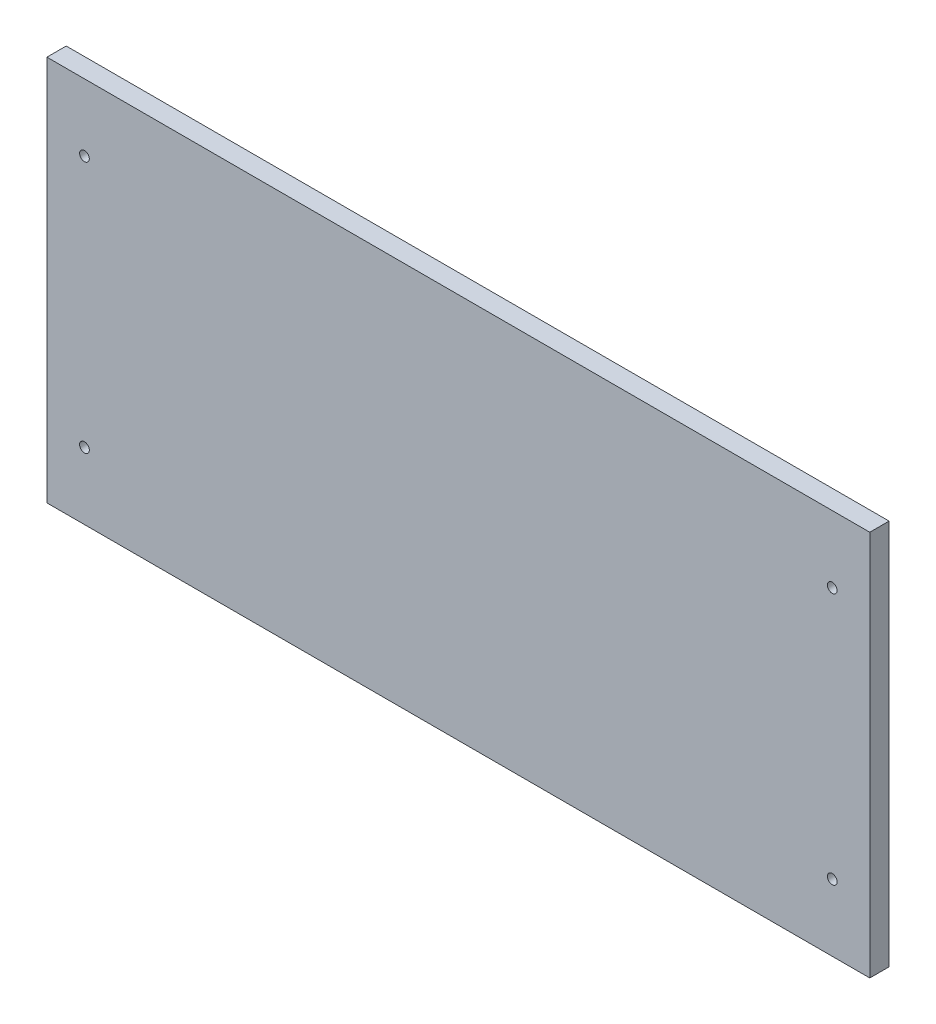
SolidWorks part; units mm, degrees
ref_plane "Front Plane" through (0, 0, 0) normal (0, 0, 1) x (1, 0, 0)
ref_plane "Top Plane" through (0, 0, 0) normal (0, 1, 0) x (1, 0, 0)
ref_plane "Right Plane" through (0, 0, 0) normal (1, 0, 0) x (0, 0, -1)
sketch "Sketch1" plane through (0, 0, 0) normal (0, 0, 1) x (1, 0, 0)
  line L0 (135.35, 127) -> (135.35, 0) construction
  line L1 (0, 0) -> (270.7, 0)
  line L2 (0, 0) -> (0, 127)
  line L3 (0, 127) -> (270.7, 127)
  line L4 (270.7, 0) -> (270.7, 127)
  line L5 (0, 63.5) -> (270.7, 63.5) construction
  circle A3 centre (12.35, 105) radius 1.6
  circle A7 centre (258.35, 105) radius 1.6
  circle A8 centre (258.35, 22) radius 1.6
  circle A9 centre (12.35, 22) radius 1.6
  dimension "D11" = 3.2
  dimension "D1" = 127
  dimension "D2" = 270.7
  dimension "D12" = 12.35
  dimension "D13" = 22
extrude "Wall" add sketch "Sketch1" along normal blind 6.35
sketch "Sketch2" plane through (0, 0, 6.35) normal (0, 0, 1) x (1, 0, 0)
  line L0 (135.35, 127) -> (135.35, 98.425) construction
  line L1 (270.7, 127) -> (0, 127) construction
  line L2 (135.35, 98.425) -> (66.6667, 98.425) construction
  line L3 (135.35, 98.425) -> (204.0333, 98.425) construction
  line L4 (0, 127) -> (0, 0) construction
  circle A0 centre (135.35, 98.425) radius 3.9687
  circle A1 centre (66.6667, 98.425) radius 3.9688
  circle A2 centre (204.0333, 98.425) radius 3.9687
  dimension "D2" = 7.9375
  dimension "D1" = 28.575
  dimension "D3" = 66.6667
extrude "RodSupportCutouts" [suppressed] cut sketch "Sketch2" against normal up to next
sketch "Sketch3" plane through (0, 0, 6.35) normal (0, 0, 1) x (1, 0, 0)
  line L1 (25.4, 88.9) -> (245.3, 88.9)
  line L2 (25.4, 88.9) -> (25.4, 114.3)
  line L3 (25.4, 114.3) -> (245.3, 114.3)
  line L4 (245.3, 88.9) -> (245.3, 114.3)
  line L5 (25.4, 88.9) -> (245.3, 114.3) construction
  line L6 (25.4, 114.3) -> (245.3, 88.9) construction
  line L7 (270.7, 127) -> (0, 127) construction
  line L8 (0, 127) -> (0, 0) construction
  point P0 (135.35, 101.6)
  point P9 (135.35, 127)
  dimension "D1" = 25.4
  dimension "D2" = 25.4
  dimension "D3" = 25.4
extrude "CannulaLargeCutout" [suppressed] cut sketch "Sketch3" against normal up to next
sketch "Sketch4" [suppressed] plane through (0, 0, 9.525) normal (0, 0, 1) x (1, 0, 0)
  line L0 (6, 103.5) -> (194, 103.5) construction
  line L1 (6, 105) -> (6, 22) construction
  line L2 (194, 105) -> (194, 22) construction
  line L3 (200, 127) -> (0, 127) construction
  line L4 (0, 127) -> (0, 0) construction
  circle A0 centre (60, 103.5) radius 6.35
  circle A1 centre (20, 103.5) radius 6.35
  circle A2 centre (100, 103.5) radius 6.35
  circle A3 centre (140, 103.5) radius 6.35
  circle A4 centre (60, 63.5) radius 6.35
  circle A5 centre (100, 63.5) radius 6.35
  circle A6 centre (140, 63.5) radius 6.35
  circle A7 centre (60, 23.5) radius 6.35
  circle A8 centre (100, 23.5) radius 6.35
  circle A9 centre (140, 23.5) radius 6.35
  circle A10 centre (20, 63.5) radius 6.35
  circle A11 centre (20, 23.5) radius 6.35
  circle A12 centre (180, 103.5) radius 6.35
  circle A13 centre (180, 63.5) radius 6.35
  circle A14 centre (180, 23.5) radius 6.35
  point P42 (100, 127)
  point P45 (0, 63.5)
  dimension "D3" = 12.7
  dimension "D1" = 5
  dimension "D2" = 3
extrude "CannulaHoles" [suppressed] cut sketch "Sketch4" against normal up to next
ref_plane "LeftBoundary" through (25.4, 0, 0) normal (-1, 0, 0) x (0, 0, 1)
ref_plane "RightBoundary" through (245.3, 0, 0) normal (1, 0, 0) x (0, 0, -1)
ref_plane "TopBoundary" through (0, 101.6, 0) normal (0, 1, 0) x (1, 0, 0)
ref_plane "BottomBoundary" through (0, 25.4, 0) normal (0, -1, 0) x (-1, 0, 0)
sketch "Sketch5" plane through (0, 0, 6.35) normal (0, 0, 1) x (1, 0, 0)
  line L4 (25.4, 3.4925) -> (25.4, -3.4925) construction
  line L5 (3.4925, 101.6) -> (-3.4925, 101.6) construction
  circle A0 centre (25.4, 101.6) radius 3.9687
  point P2 (0, 0)
  point P6 (-57.4643, 172.6109)
  dimension "D1" = 7.9375
extrude "RodSupportCutout" [suppressed] cut sketch "Sketch5" against normal up to next
pattern_linear "SupportPattern" [suppressed] count 7 spacing 36.65 count 5 spacing 19.05 of bodies 105
equation "\"Length\"= 283mm"
equation "\"Width\"= 225mm"
equation "\"WallThickness\"= 0.25in"
equation "\"UpperWaterJacketThickness\"= 28mm"
equation "\"SpacerHeight\"= 80.2mm"
equation "\"SpacerCornerWidth\"= 10mm"
equation "\"SpacerCornerHeight\"= 60.16mm"
equation "\"SpacerPegDiameter\"= 10mm"
equation "\"SpacerPegHeight\"= 10mm"
equation "\"TubingShort\"= 110mm"
equation "\"TubingLong\"= 175mm"
equation "\"PlateLength\"= 252mm"
equation "\"PlateWidth\"= 190mm"
equation "\"PlateHoleDiameter\"= 5.9mm"
equation "\"PlateHoleBottom\"= 2mm"
equation "\"PlateHoleSide\"= 1.55mm"
equation "\"PlateHoleSpacing\"= 3.1mm"
equation "\"PlateThickness\"= 1.55mm"
equation "\"ReservoirBottom\"= 12.5mm"
equation "\"ReservoirSupportWidth\"= 12mm"
equation "\"ReservoirSupportHeight\"= 15.1mm"
equation "\"ReservoirSupportPlacementHeight\"= 50mm"
equation "\"ReservoirHoleDiameter\"= 12.7mm"
equation "\"ReservoirHoleRight\"= 25mm"
equation "\"ReservoirHoleTop\"= \"ReservoirSupportPlacementHeight\""
equation "\"ReservoirHeight\"= 90mm"
equation "\"ReservoirPortBottom\"= 4mm"
equation "\"ReservoirPortTop\"= 10mm"
equation "\"ReservoirPortWidth\"= 101mm"
equation "\"CustomSpacerHeight\"= 5in"
equation "\"CustomSpacerRodHoleHeight\"= .75in"
equation "\"CustomSpacerRodHoleDiameter\"= .3125in"
equation "\"ScrewBlockSide\"= 12mm"
equation "\"ScrewBlockUpperHeight\"= 16mm"
equation "\"ScrewBlockLowerHeight\"= 16mm"
equation "\"InternalLength\"= 258mm"
equation "\"InternalWidth\"= 200mm"
equation "\"CustomSpacerPegHeight\"= 1in"
equation "\"CustomSpacerScrewBore\"=3.2mm"
equation "\"CustomSpacerScrewDepth\"=10mm"
equation "\"D1@Sketch1\"=\"CustomSpacerHeight\""
equation "\"D2@Sketch1\"=\"WallLength\""
equation "\"D11@Sketch1\"=\"CustomSpacerScrewBore\""
equation "\"D12@Sketch1\"  = \"ScrewBlockSide\"/2 + \"WallThickness\""
equation "\"D13@Sketch1\"=\"ScrewBlockUpperHeight\"+\"ScrewBlockSide\"/2"
equation "\"D1@Wall\" = \"WallThickness\""
equation "\"D1@Sketch2\"=\"CustomSpacerRodHoleHeight\" + \"CustomSpacerRodHoleDiameter\" +0.0625in"
equation "\"D2@Sketch2\"=\"CustomSpacerRodHoleDiameter\""
equation "\"D3@Sketch2\"=\"InternalWidth\" / 3"
equation "\"D1@Sketch3\"=1in"
equation "\"WallLength\" = \"InternalLength\" + ( 2 * \"WallThickness\" )"
equation "\"D1@Sketch5\"=\"CustomSpacerRodHoleDiameter\""
